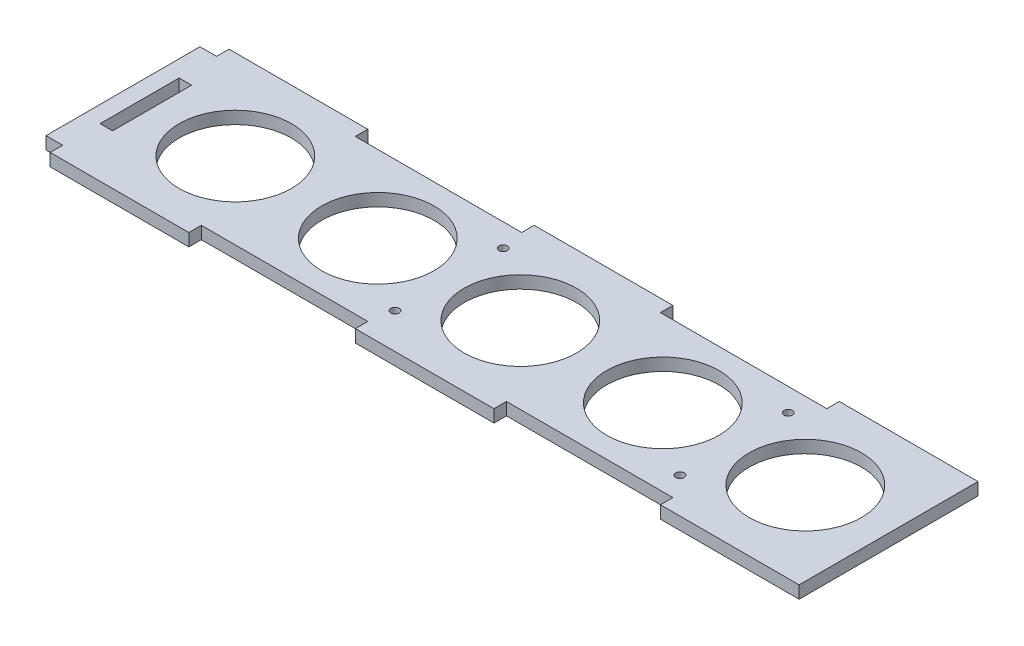
SolidWorks part; units mm, degrees
ref_plane "Front Plane" through (0, 0, 0) normal (0, 0, 1) x (1, 0, 0)
ref_plane "Top Plane" through (0, 0, 0) normal (0, 1, 0) x (1, 0, 0)
ref_plane "Right Plane" through (0, 0, 0) normal (1, 0, 0) x (0, 0, -1)
sketch "Sketch1" plane through (0, 0, 0) normal (0, 1, 0) x (1, 0, 0)
  line L0 (73.3333, 18.5) -> (106.6667, 18.5) construction
  line L1 (0, 21.5) -> (180, 21.5)
  line L2 (0, 21.5) -> (0, -21.5)
  line L3 (0, -21.5) -> (180, -21.5)
  line L4 (180, 21.5) -> (180, -21.5)
  line L5 (0, -9.5) -> (3, -9.5)
  line L6 (0, -9.5) -> (0, 9.5)
  line L7 (0, 9.5) -> (3, 9.5)
  line L8 (3, -9.5) -> (3, 9.5)
  line L9 (33.3333, 21.5) -> (73.3333, 21.5)
  line L10 (33.3333, 21.5) -> (33.3333, 18.5)
  line L11 (33.3333, 18.5) -> (73.3333, 18.5)
  line L12 (73.3333, 21.5) -> (73.3333, 18.5)
  line L13 (106.6667, 21.5) -> (146.6667, 21.5)
  line L14 (106.6667, 21.5) -> (106.6667, 18.5)
  line L15 (106.6667, 18.5) -> (146.6667, 18.5)
  line L16 (146.6667, 21.5) -> (146.6667, 18.5)
  line L17 (146.6667, 18.5) -> (180, 18.5) construction
  line L18 (33.3333, 18.5) -> (0, 18.5) construction
  line L19 (74.375, 0) -> (74.375, 13) construction
  line L20 (106.6667, -18.5) -> (146.6667, -18.5)
  line L21 (146.6667, -21.5) -> (146.6667, -18.5)
  line L22 (106.6667, -21.5) -> (146.6667, -21.5)
  line L23 (106.6667, -21.5) -> (106.6667, -18.5)
  line L24 (33.3333, -18.5) -> (73.3333, -18.5)
  line L25 (73.3333, -21.5) -> (73.3333, -18.5)
  line L26 (33.3333, -21.5) -> (73.3333, -21.5)
  line L27 (33.3333, -21.5) -> (33.3333, -18.5)
  line L28 (23, 0) -> (57.25, 0) construction
  line L29 (57.25, 0) -> (91.5, 0) construction
  line L30 (91.5, 0) -> (125.75, 0) construction
  line L31 (125.75, 0) -> (160, 0) construction
  line L32 (0, 18.5) -> (-4, 18.5)
  line L33 (0, 18.5) -> (0, -18.5)
  line L34 (0, -18.5) -> (-4, -18.5)
  line L35 (-4, 18.5) -> (-4, -18.5)
  line L36 (142.875, 0) -> (142.875, 13) construction
  circle A0 centre (23, 0) radius 13.5
  circle A1 centre (57.25, 0) radius 13.5
  circle A2 centre (91.5, 0) radius 13.5
  circle A3 centre (125.75, 0) radius 13.5
  circle A4 centre (160, 0) radius 13.5
  circle A5 centre (74.375, 13) radius 1
  circle A6 centre (142.875, 13) radius 1
  circle A7 centre (142.875, -13) radius 1
  circle A8 centre (74.375, -13) radius 1
  point P4 (0, 0)
  point P11 (3, 0)
  dimension "D6" = 23
  dimension "D7" = 27
  dimension "D10" = 13
  dimension "D11" = 2
  dimension "D12" = 2
  dimension "D1" = 43
  dimension "D2" = 180
  dimension "D3" = 19
  dimension "D4" = 3
  dimension "D5" = 40
  dimension "D8" = 20
  dimension "D9" = 4
  dimension "D13" = 13
extrude "Boss-Extrude1" add sketch "Sketch1" along normal blind 3 contours L3 L27 L24 L25 L23 L20 L21 L4 L1 L16 L15 L14 L12 L11 L10 L2 L7 L8 L5 A4 A3 A2 A1 A0 | L33 L32 L35 L34 region at (16.6667, 0, -19.6494)
